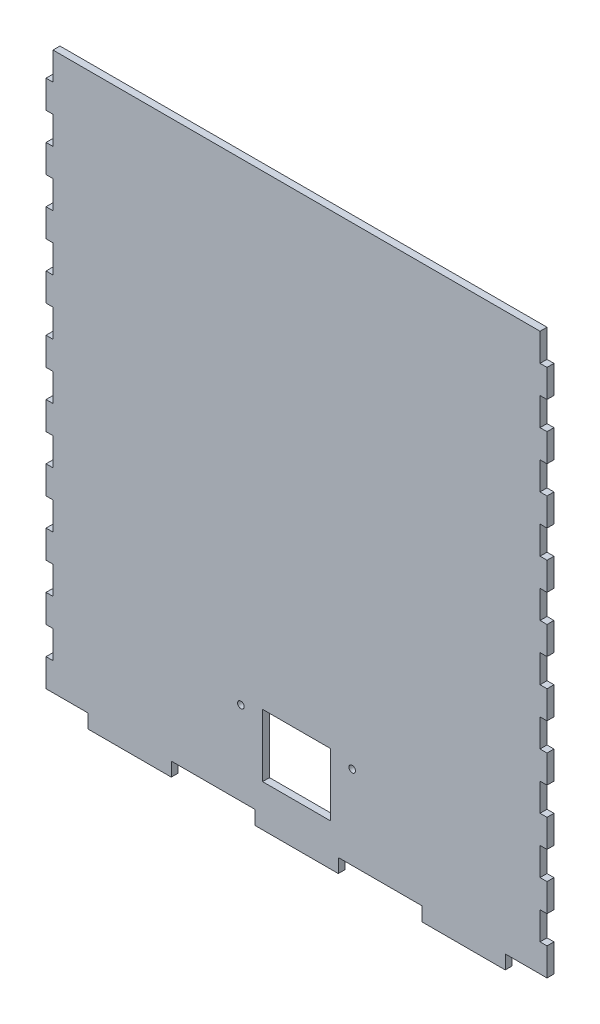
SolidWorks part; units mm, degrees
material "Acrylic (Medium-high impact)"
ref_plane "Front Plane" through (0, 0, 0) normal (0, 0, 1) x (1, 0, 0)
ref_plane "Top Plane" through (0, 0, 0) normal (0, 1, 0) x (1, 0, 0)
ref_plane "Right Plane" through (0, 0, 0) normal (1, 0, 0) x (0, 0, -1)
sketch "Sketch1" plane through (0, 0, 0) normal (0, 0, 1) x (1, 0, 0)
  line L0 (-114.3, 114.3) -> (-111.125, 114.3)
  line L1 (-114.3, 127) -> (114.3, 127)
  line L2 (-114.3, 127) -> (-114.3, -127)
  line L3 (-114.3, -127) -> (114.3, -127)
  line L4 (114.3, 127) -> (114.3, -127)
  line L5 (-114.3, 127) -> (-111.125, 127)
  line L6 (-114.3, 127) -> (-114.3, 114.3)
  line L7 (-114.3, 114.3) -> (-111.125, 114.3)
  line L8 (-111.125, 127) -> (-111.125, 114.3)
  line L9 (-114.3, 114.3) -> (-114.3, 101.6)
  line L10 (-114.3, 101.6) -> (-111.125, 101.6)
  line L11 (-111.125, 114.3) -> (-111.125, 101.6)
  line L12 (-114.3, 101.6) -> (-111.125, 101.6)
  line L13 (-114.3, 101.6) -> (-114.3, 88.9)
  line L14 (-114.3, 88.9) -> (-111.125, 88.9)
  line L15 (-111.125, 101.6) -> (-111.125, 88.9)
  line L16 (-114.3, 88.9) -> (-111.125, 88.9)
  line L17 (-114.3, 88.9) -> (-114.3, 76.2)
  line L18 (-114.3, 76.2) -> (-111.125, 76.2)
  line L19 (-111.125, 88.9) -> (-111.125, 76.2)
  line L20 (-114.3, 76.2) -> (-111.125, 76.2)
  line L21 (-114.3, 76.2) -> (-114.3, 63.5)
  line L22 (-114.3, 63.5) -> (-111.125, 63.5)
  line L23 (-111.125, 76.2) -> (-111.125, 63.5)
  line L24 (-114.3, 63.5) -> (-111.125, 63.5)
  line L25 (-114.3, 63.5) -> (-114.3, 50.8)
  line L26 (-114.3, 50.8) -> (-111.125, 50.8)
  line L27 (-111.125, 63.5) -> (-111.125, 50.8)
  line L28 (-114.3, 50.8) -> (-111.125, 50.8)
  line L29 (-114.3, 50.8) -> (-114.3, 38.1)
  line L30 (-114.3, 38.1) -> (-111.125, 38.1)
  line L31 (-111.125, 50.8) -> (-111.125, 38.1)
  line L32 (-114.3, 38.1) -> (-111.125, 38.1)
  line L33 (-114.3, 38.1) -> (-114.3, 25.4)
  line L34 (-114.3, 25.4) -> (-111.125, 25.4)
  line L35 (-111.125, 38.1) -> (-111.125, 25.4)
  line L36 (-114.3, 25.4) -> (-111.125, 25.4)
  line L37 (-114.3, 25.4) -> (-114.3, 12.7)
  line L38 (-114.3, 12.7) -> (-111.125, 12.7)
  line L39 (-111.125, 25.4) -> (-111.125, 12.7)
  line L40 (-114.3, 12.7) -> (-111.125, 12.7)
  line L41 (-114.3, 12.7) -> (-114.3, 0)
  line L42 (-114.3, 0) -> (-111.125, 0)
  line L43 (-111.125, 12.7) -> (-111.125, 0)
  line L44 (-114.3, 0) -> (-111.125, 0)
  line L45 (-114.3, 0) -> (-114.3, -12.7)
  line L46 (-114.3, -12.7) -> (-111.125, -12.7)
  line L47 (-111.125, 0) -> (-111.125, -12.7)
  line L48 (-114.3, -12.7) -> (-111.125, -12.7)
  line L49 (-114.3, -12.7) -> (-114.3, -25.4)
  line L50 (-114.3, -25.4) -> (-111.125, -25.4)
  line L51 (-111.125, -12.7) -> (-111.125, -25.4)
  line L52 (-114.3, -25.4) -> (-111.125, -25.4)
  line L53 (-114.3, -25.4) -> (-114.3, -38.1)
  line L54 (-114.3, -38.1) -> (-111.125, -38.1)
  line L55 (-111.125, -25.4) -> (-111.125, -38.1)
  line L56 (-114.3, -38.1) -> (-111.125, -38.1)
  line L57 (-114.3, -38.1) -> (-114.3, -50.8)
  line L58 (-114.3, -50.8) -> (-111.125, -50.8)
  line L59 (-111.125, -38.1) -> (-111.125, -50.8)
  line L60 (-114.3, -50.8) -> (-111.125, -50.8)
  line L61 (-114.3, -50.8) -> (-114.3, -63.5)
  line L62 (-114.3, -63.5) -> (-111.125, -63.5)
  line L63 (-111.125, -50.8) -> (-111.125, -63.5)
  line L64 (-114.3, -63.5) -> (-111.125, -63.5)
  line L65 (-114.3, -63.5) -> (-114.3, -76.2)
  line L66 (-114.3, -76.2) -> (-111.125, -76.2)
  line L67 (-111.125, -63.5) -> (-111.125, -76.2)
  line L68 (-114.3, -76.2) -> (-111.125, -76.2)
  line L69 (-114.3, -76.2) -> (-114.3, -88.9)
  line L70 (-114.3, -88.9) -> (-111.125, -88.9)
  line L71 (-111.125, -76.2) -> (-111.125, -88.9)
  line L72 (-114.3, -88.9) -> (-111.125, -88.9)
  line L73 (-114.3, -88.9) -> (-114.3, -101.6)
  line L74 (-114.3, -101.6) -> (-111.125, -101.6)
  line L75 (-111.125, -88.9) -> (-111.125, -101.6)
  line L76 (-114.3, -101.6) -> (-111.125, -101.6)
  line L77 (-114.3, -101.6) -> (-114.3, -114.3)
  line L78 (-114.3, -114.3) -> (-111.125, -114.3)
  line L79 (-111.125, -101.6) -> (-111.125, -114.3)
  line L80 (-114.3, -114.3) -> (-111.125, -114.3)
  line L81 (-114.3, -114.3) -> (-114.3, -127)
  line L82 (-114.3, -127) -> (-111.125, -127)
  line L83 (-111.125, -114.3) -> (-111.125, -127)
  line L100 (0, 127) -> (0, -127) construction
  line L101 (114.3, 114.3) -> (111.125, 114.3)
  line L102 (114.3, 127) -> (111.125, 127)
  line L103 (114.3, 127) -> (114.3, 114.3)
  line L104 (114.3, 114.3) -> (111.125, 114.3)
  line L105 (111.125, 127) -> (111.125, 114.3)
  line L106 (114.3, 114.3) -> (114.3, 101.6)
  line L107 (114.3, 101.6) -> (111.125, 101.6)
  line L108 (111.125, 114.3) -> (111.125, 101.6)
  line L109 (114.3, 101.6) -> (111.125, 101.6)
  line L110 (114.3, 101.6) -> (114.3, 88.9)
  line L111 (114.3, 88.9) -> (111.125, 88.9)
  line L112 (111.125, 101.6) -> (111.125, 88.9)
  line L113 (114.3, 88.9) -> (111.125, 88.9)
  line L114 (114.3, 88.9) -> (114.3, 76.2)
  line L115 (114.3, 76.2) -> (111.125, 76.2)
  line L116 (111.125, 88.9) -> (111.125, 76.2)
  line L117 (114.3, 76.2) -> (111.125, 76.2)
  line L118 (114.3, 76.2) -> (114.3, 63.5)
  line L119 (114.3, 63.5) -> (111.125, 63.5)
  line L120 (111.125, 76.2) -> (111.125, 63.5)
  line L121 (114.3, 63.5) -> (111.125, 63.5)
  line L122 (114.3, 63.5) -> (114.3, 50.8)
  line L123 (114.3, 50.8) -> (111.125, 50.8)
  line L124 (111.125, 63.5) -> (111.125, 50.8)
  line L125 (114.3, 50.8) -> (111.125, 50.8)
  line L126 (114.3, 50.8) -> (114.3, 38.1)
  line L127 (114.3, 38.1) -> (111.125, 38.1)
  line L128 (111.125, 50.8) -> (111.125, 38.1)
  line L129 (114.3, 38.1) -> (111.125, 38.1)
  line L130 (114.3, 38.1) -> (114.3, 25.4)
  line L131 (114.3, 25.4) -> (111.125, 25.4)
  line L132 (111.125, 38.1) -> (111.125, 25.4)
  line L133 (114.3, 25.4) -> (111.125, 25.4)
  line L134 (114.3, 25.4) -> (114.3, 12.7)
  line L135 (114.3, 12.7) -> (111.125, 12.7)
  line L136 (111.125, 25.4) -> (111.125, 12.7)
  line L137 (114.3, 12.7) -> (111.125, 12.7)
  line L138 (114.3, 12.7) -> (114.3, 0)
  line L139 (114.3, 0) -> (111.125, 0)
  line L140 (111.125, 12.7) -> (111.125, 0)
  line L141 (114.3, 0) -> (111.125, 0)
  line L142 (114.3, 0) -> (114.3, -12.7)
  line L143 (114.3, -12.7) -> (111.125, -12.7)
  line L144 (111.125, 0) -> (111.125, -12.7)
  line L145 (114.3, -12.7) -> (111.125, -12.7)
  line L146 (114.3, -12.7) -> (114.3, -25.4)
  line L147 (114.3, -25.4) -> (111.125, -25.4)
  line L148 (111.125, -12.7) -> (111.125, -25.4)
  line L149 (114.3, -25.4) -> (111.125, -25.4)
  line L150 (114.3, -25.4) -> (114.3, -38.1)
  line L151 (114.3, -38.1) -> (111.125, -38.1)
  line L152 (111.125, -25.4) -> (111.125, -38.1)
  line L153 (114.3, -38.1) -> (111.125, -38.1)
  line L154 (114.3, -38.1) -> (114.3, -50.8)
  line L155 (114.3, -50.8) -> (111.125, -50.8)
  line L156 (111.125, -38.1) -> (111.125, -50.8)
  line L157 (114.3, -50.8) -> (111.125, -50.8)
  line L158 (114.3, -50.8) -> (114.3, -63.5)
  line L159 (114.3, -63.5) -> (111.125, -63.5)
  line L160 (111.125, -50.8) -> (111.125, -63.5)
  line L161 (114.3, -63.5) -> (111.125, -63.5)
  line L162 (114.3, -63.5) -> (114.3, -76.2)
  line L163 (114.3, -76.2) -> (111.125, -76.2)
  line L164 (111.125, -63.5) -> (111.125, -76.2)
  line L165 (114.3, -76.2) -> (111.125, -76.2)
  line L166 (114.3, -76.2) -> (114.3, -88.9)
  line L167 (114.3, -88.9) -> (111.125, -88.9)
  line L168 (111.125, -76.2) -> (111.125, -88.9)
  line L169 (114.3, -88.9) -> (111.125, -88.9)
  line L170 (114.3, -88.9) -> (114.3, -101.6)
  line L171 (114.3, -101.6) -> (111.125, -101.6)
  line L172 (111.125, -88.9) -> (111.125, -101.6)
  line L173 (114.3, -101.6) -> (111.125, -101.6)
  line L174 (114.3, -101.6) -> (114.3, -114.3)
  line L175 (114.3, -114.3) -> (111.125, -114.3)
  line L176 (111.125, -101.6) -> (111.125, -114.3)
  line L177 (114.3, -114.3) -> (111.125, -114.3)
  line L178 (114.3, -114.3) -> (114.3, -127)
  line L179 (114.3, -127) -> (111.125, -127)
  line L180 (111.125, -114.3) -> (111.125, -127)
  line L186 (95.25, -127) -> (95.25, -133.35)
  line L187 (95.25, -133.35) -> (57.15, -133.35)
  line L188 (57.15, -133.35) -> (57.15, -127)
  line L189 (57.15, -127) -> (95.25, -127)
  line L191 (-19.05, -127) -> (19.05, -127)
  line L192 (19.05, -127) -> (19.05, -133.35)
  line L193 (19.05, -133.35) -> (-19.05, -133.35)
  line L194 (-19.05, -133.35) -> (-19.05, -127)
  line L195 (-95.25, -127) -> (-57.15, -127)
  line L196 (-57.15, -127) -> (-57.15, -133.35)
  line L197 (-57.15, -133.35) -> (-95.25, -133.35)
  line L198 (-95.25, -133.35) -> (-95.25, -127)
  point P4 (0, 127)
  point P6 (-114.3, 0)
  dimension "D1" = 254
  dimension "D2" = 228.6
  dimension "D3" = 12.7
  dimension "D4" = 3.175
  dimension "D7" = 6.35
  dimension "D8" = 38.1
  dimension "D9" = 19.05
  dimension "D5" = 20
  dimension "D6" = 20
  dimension "D10" = 3
extrude "Boss-Extrude1" add sketch "Sketch1" along normal blind 3.175
sketch "Sketch2" plane through (0, 0, 3.175) normal (0, 0, 1) x (1, 0, 0)
  line L0 (-25.4, -88.9) -> (25.4, -88.9) construction
  line L1 (0, -85.725) -> (0, -114.3) construction
  line L2 (-15.5, -85.725) -> (15.5, -85.725)
  line L3 (-15.5, -85.725) -> (-15.5, -114.3)
  line L5 (95.25, -127) -> (114.3, -127) construction
  line L8 (-15.5, -114.3) -> (15.5, -114.3)
  line L9 (15.5, -85.725) -> (15.5, -114.3)
  line L12 (-114.3, -114.3) -> (-114.3, -127) construction
  circle A0 centre (-25.4, -88.9) radius 1.5
  circle A1 centre (25.4, -88.9) radius 1.5
  point P12 (0, -88.9)
  dimension "D1" = 3
  dimension "D2" = 50.8
  dimension "D3" = 31
  dimension "D4" = 25.4
  dimension "D5" = 28.575
  dimension "D6" = 12.7
  dimension "D7" = 114.3
extrude "Cut-Extrude1" cut sketch "Sketch2" against normal through all
